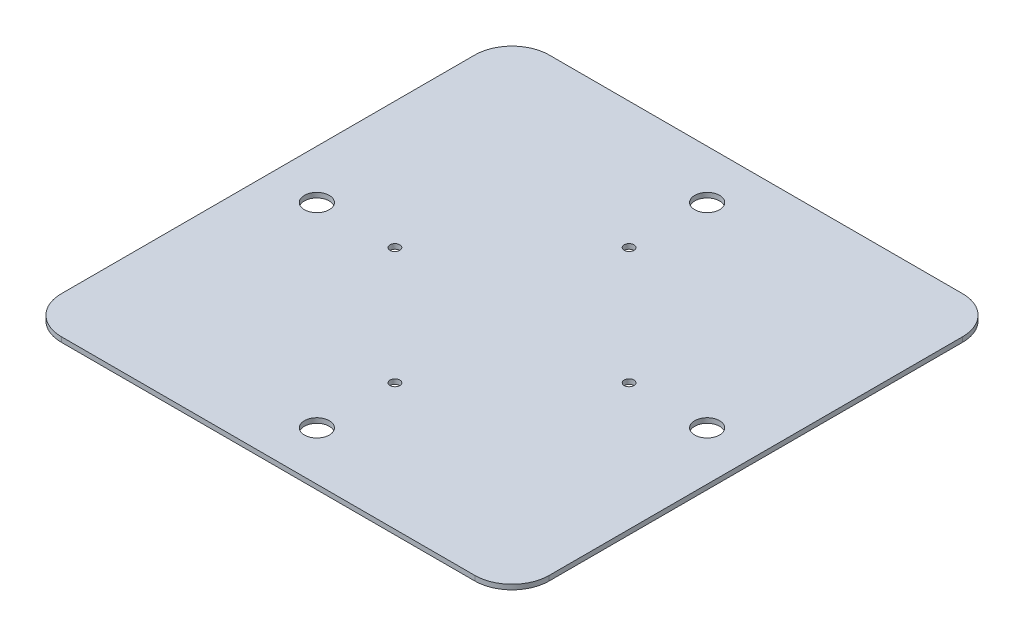
SolidWorks part; units mm, degrees
ref_plane "Front Plane" through (0, 0, 0) normal (0, 0, 1) x (1, 0, 0)
ref_plane "Top Plane" through (0, 0, 0) normal (0, 1, 0) x (1, 0, 0)
ref_plane "Right Plane" through (0, 0, 0) normal (1, 0, 0) x (0, 0, -1)
sketch "Sketch1" plane through (0, 0, 0) normal (0, 1, 0) x (1, 0, 0)
  line L1 (-42.38, -50) -> (42.38, -50)
  line L2 (-50, -42.38) -> (-50, 42.38)
  line L3 (-42.38, 50) -> (42.38, 50)
  line L4 (50, -42.38) -> (50, 42.38)
  line L5 (-50, -50) -> (50, 50) construction
  line L6 (-50, 50) -> (50, -50) construction
  arc A0 (42.38, 50) -> (50, 42.38) centre (42.38, 42.38) cw
  arc A1 (-50, 42.38) -> (-42.38, 50) centre (-42.38, 42.38) cw
  arc A2 (-42.38, -50) -> (-50, -42.38) centre (-42.38, -42.38) cw
  arc A3 (42.38, -50) -> (50, -42.38) centre (42.38, -42.38) ccw
  point P0 (0, 0)
  dimension "D3" = 7.62
  dimension "D1" = 100
  dimension "D2" = 100
extrude "Boss-Extrude1" add sketch "Sketch1" along normal blind 1
sketch "Sketch2" plane through (0, 1, 0) normal (0, 1, 0) x (1, 0, 0)
  circle A0 centre (0, 40) radius 2.55
  circle A2 centre (40, 0) radius 2.55
  circle A4 centre (0, -40) radius 2.55
  circle A6 centre (-40, 0) radius 2.55
  point P20 (0, 0)
  dimension "D1" = 40
  dimension "D2" = 5.1
  dimension "D3" = 5.1
  dimension "D4" = 5.1
  dimension "D5" = 5.1
extrude "Cut-Extrude6" cut sketch "Sketch2" against normal blind 2.54
sketch "Sketch3" plane through (0, 1, 0) normal (0, 1, 0) x (1, 0, 0)
  line L0 (0, 0) -> (0, 24) construction
  circle A0 centre (0, 24) radius 1
  circle A1 centre (24, 0) radius 1
  circle A2 centre (0, -24) radius 1
  circle A3 centre (-24, 0) radius 1
  point P13 (0, 0)
  dimension "D1" = 24
extrude "Cut-Extrude7" cut sketch "Sketch3" against normal blind 2.54
sketch3d "3DSketch2"
  line L0 (0, 0, 0) -> (0, 11.5021, 0) construction
ref_axis "Axis1" through (0, 0, 0) along (0, 1, 0)
